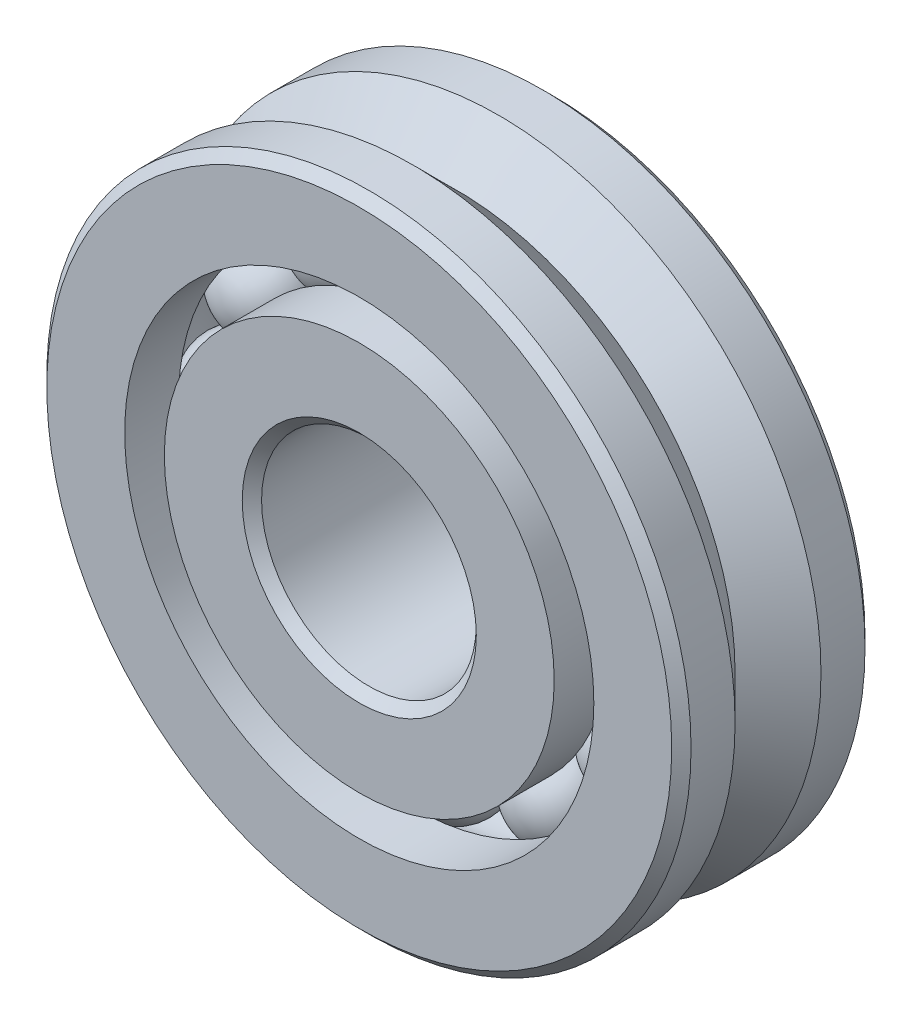
SolidWorks part; units mm, degrees
ref_plane "Front Plane" through (0, 0, 0) normal (0, 0, 1) x (1, 0, 0)
ref_plane "Top Plane" through (0, 0, 0) normal (0, 1, 0) x (1, 0, 0)
ref_plane "Right Plane" through (0, 0, 0) normal (1, 0, 0) x (0, 0, -1)
sketch "Sketch1" plane through (0, 0, 0) normal (1, 0, 0) x (0, 0, -1)
  line L0 (-4.5, 0) -> (4.5, 0) construction
  line L1 (0, 13) -> (0, -15) construction
  line L2 (4.05, 15) -> (2, 15)
  line L3 (-4.05, 15) -> (-4.5, 14.55)
  line L4 (-4.5, 14.55) -> (-4.5, 10.9231)
  line L5 (-4.5, 10.9231) -> (-2, 10.9231)
  line L6 (4.5, 10.9231) -> (2, 10.9231)
  line L7 (4.5, 14.55) -> (4.5, 10.9231)
  line L8 (4.05, 15) -> (4.5, 14.55)
  line L9 (0, 15) -> (0, 10) construction
  line L10 (0, 10) -> (0, 5) construction
  line L12 (2, 15) -> (0, 13)
  line L13 (0, 13) -> (-2, 15)
  line L14 (-2, 15) -> (-4.05, 15)
  arc A0 (-2, 10.9231) -> (2, 10.9231) centre (0, 10) cw
  point P14 (0, 5)
  point P15 (-2, 15)
  point P17 (2, 15)
  dimension "Width" = 9
  dimension "OD" = 30
  dimension "D1" = 45
  dimension "D2" = 0.45
  dimension "Shaft Dia" = 10
  dimension "D3" = 4
  dimension "D4" = 0.9231
  dimension "D5" = 4
  dimension "D6" = 2
revolve "Revolve1" add sketch "Sketch1" angle 360 about L0
sketch "Sketch3" plane through (0, 0, 0) normal (1, 0, 0) x (0, 0, -1)
  line L0 (-4.5, 9.0769) -> (-2, 9.0769)
  line L1 (0, 13) -> (0, -15) construction
  line L2 (-4.5, 14.55) -> (-4.5, 10.9231) construction
  line L3 (-4.5, 9.0769) -> (-4.5, 5.45)
  line L4 (-4.05, 15) -> (-4.5, 14.55) construction
  line L5 (-4.5, 5.45) -> (-4.05, 5)
  line L6 (-4.05, 5) -> (4.05, 5)
  line L7 (4.05, 15) -> (4.05, -15) construction
  line L8 (4.05, 5) -> (4.5, 5.45)
  line L9 (4.5, -14.55) -> (4.5, 14.55) construction
  line L10 (4.5, 5.45) -> (4.5, 9.0769)
  line L11 (4.5, 9.0769) -> (2, 9.0769)
  line L13 (4.05, 15) -> (4.5, 14.55) construction
  arc A0 (2, 10.9231) -> (-2, 10.9231) centre (0, 10) ccw construction
  arc A1 (2, 9.0769) -> (-2, 9.0769) centre (0, 10) cw
revolve "Revolve3" add sketch "Sketch3" angle 360 about L0
sketch "Sketch4" plane through (0, 0, 0) normal (1, 0, 0) x (0, 0, -1)
  line L0 (-2.2027, 10) -> (2.2027, 10)
  arc A2 (-2.2027, 10) -> (2.2027, 10) centre (0, 10) cw
  arc A3 (2, 10.9231) -> (-2, 10.9231) centre (0, 10) ccw construction
revolve "Revolve4" add sketch "Sketch4" angle 360 about L0
ref_axis "Axis1" through (0, 0, -4.5) along (0, 0, 1)
pattern_circular "CirPattern1" count 12 every 30 about axis through (0, 0, -4.5) along (0, 0, 1) of bodies 104
sketch "Sketch5" plane through (0, 0, 0) normal (1, 0, 0) x (0, 0, -1)
  line L0 (-4.5, 10.9231) -> (-2, 10.9231) construction
  line L1 (-4.275, 10.9231) -> (-2.2027, 10.9231)
  line L2 (-4.275, 10.9231) -> (-4.275, 9.0769)
  line L3 (-4.275, 9.0769) -> (-2.2027, 9.0769)
  line L4 (-2.2027, 10.9231) -> (-2.2027, 9.0769)
  line L5 (-4.5, 9.0769) -> (-2, 9.0769) construction
  line L6 (4.5, 10.9231) -> (2, 10.9231) construction
  line L7 (4.275, 10.9231) -> (2.2027, 10.9231)
  line L8 (4.275, 10.9231) -> (4.275, 9.0769)
  line L9 (4.275, 9.0769) -> (2.2027, 9.0769)
  line L10 (2.2027, 10.9231) -> (2.2027, 9.0769)
  line L11 (4.5, 9.0769) -> (2, 9.0769) construction
  line L12 (-4.05, 15) -> (-4.5, 14.55) construction
  point P18 (-4.275, 14.775)
equation "\"D2@Sketch1\" = \"Width@Sketch1\"*.05"
equation "\"D3@Sketch1\" = \"Width@Sketch1\"/2.25"
equation "\"D4@Sketch1\" = (((\"OD@Sketch1\"-\"Width@Sketch1\")/2)/3.25)/3.5"
equation "\"D2@CirPattern1\" = 360/\"Balls@CirPattern1\""
